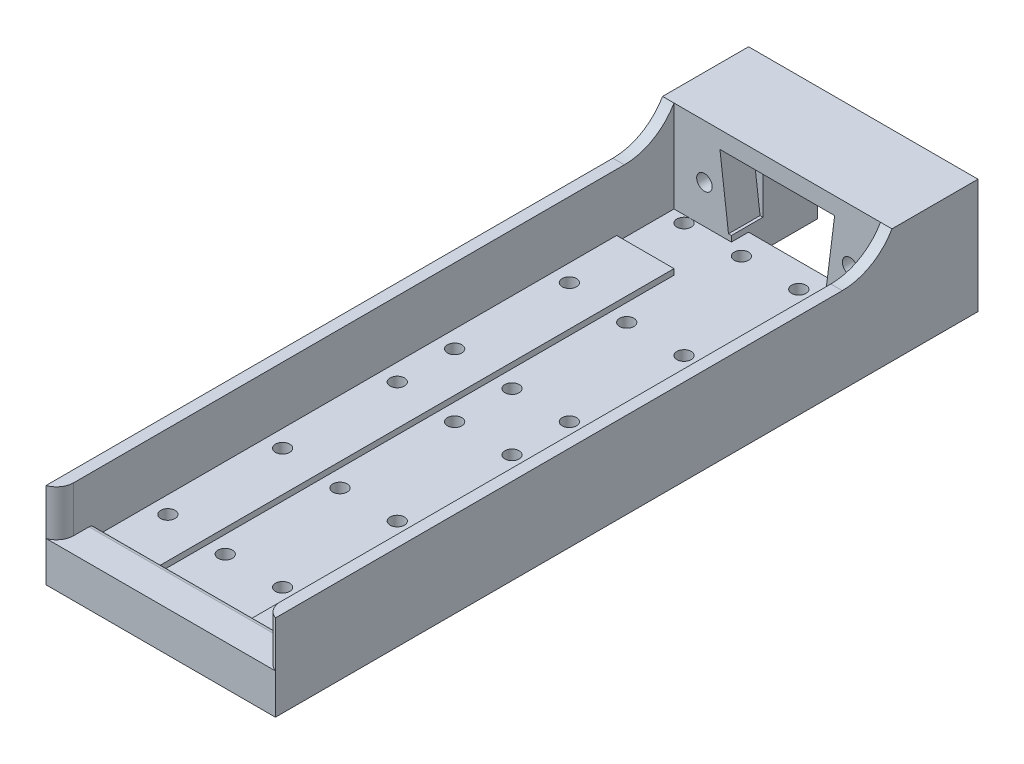
SolidWorks part; units mm, degrees
ref_plane "Front Plane" through (0, 0, 0) normal (0, 0, 1) x (1, 0, 0)
ref_plane "Top Plane" through (0, 0, 0) normal (0, 1, 0) x (1, 0, 0)
ref_plane "Right Plane" through (0, 0, 0) normal (1, 0, 0) x (0, 0, -1)
sketch "Esquisse1" plane through (0, 0, 0) normal (0, 0, 1) x (1, 0, 0)
  line L0 (18, 15) -> (20, 15)
  line L1 (20, 15) -> (20, 0)
  line L2 (20, 0) -> (-20, 0)
  line L3 (-20, 0) -> (-20, 15)
  line L4 (-20, 15) -> (-18, 15)
  line L5 (-18, 15) -> (-18, 5)
  line L6 (-18, 5) -> (-8, 5)
  line L7 (18, 5) -> (18, 15)
  line L8 (-8, 5) -> (-8, 4)
  line L9 (-8, 4) -> (8, 4)
  line L10 (8, 4) -> (8, 5)
  line L11 (8, 5) -> (18, 5)
  point P13 (0, 0)
  point P14 (0, 0)
  dimension "D1" = 2
  dimension "D2" = 1
  dimension "D3" = 36
  dimension "D4" = 10
  dimension "D5" = 2
  dimension "D6" = 40
  dimension "D7" = 5
  dimension "D8" = 10
  dimension "D9" = 4
extrude "Main" add sketch "Esquisse1" along normal mid plane 122.5
fillet "Front Conge" radius 3 2 edges at (18, 10, 61.25) (-18, 10, 61.25)
ref_plane "PlaneForDSub" through (0, 0, -46.25) normal (0, 0, 1) x (1, 0, 0)
sketch "Esquisse11" plane through (0, 0, -46.25) normal (0, 0, -1) x (-1, 0, 0)
  line L0 (20, 15) -> (20, 0) construction
  line L1 (-20, 20) -> (-18, 20)
  line L2 (-20, 20) -> (-20, 5)
  line L3 (-20, 5) -> (-18, 5)
  line L4 (-18, 20) -> (-18, 5)
  line L5 (18, 20) -> (20, 20)
  line L6 (18, 20) -> (18, 5)
  line L7 (18, 5) -> (20, 5)
  line L8 (20, 20) -> (20, 5)
  line L9 (-20, 0) -> (-20, 5) construction
  dimension "D1" = 15
extrude "DSub-Extrusion Attachment" add sketch "Esquisse11" along normal blind 15
sketch "Esquisse12" plane through (0, 0, -46.25) normal (0, 0, -1) x (-1, 0, 0)
  line L1 (-20, 20) -> (20, 20)
  line L2 (-20, 20) -> (-20, 5)
  line L3 (-20, 5) -> (20, 5)
  line L4 (20, 20) -> (20, 5)
  line L6 (20, 5) -> (20, 0) construction
  line L7 (-8, 14.175) -> (8, 14.175)
  line L8 (-8, 14.175) -> (-8, 7.175)
  line L9 (-8, 7.175) -> (8, 7.175)
  line L10 (8, 14.175) -> (8, 7.175)
  line L11 (18, 15) -> (18, 5) construction
  line L12 (-18, 5) -> (-18, 15) construction
  line L13 (-20, 0) -> (-20, 5) construction
  circle A0 centre (-12.7, 10.675) radius 1.35
  circle A1 centre (12.7, 10.675) radius 1.35
  point P20 (0, 7.175)
  point P22 (-8, 10.675)
  point P27 (18, 10)
  dimension "D5" = 2.7
  dimension "D1" = 15
  dimension "D2" = 7
  dimension "D3" = 16
  dimension "D4" = 5.3
  dimension "D6" = 25.4
  dimension "D7" = 12.7
  dimension "D8" = 5.675
  dimension "D9" = 5.3
extrude "DSub-Extrusion" add sketch "Esquisse12" along normal blind 15
sketch "Esquisse13" plane through (0, 0, -46.25) normal (0, 0, 1) x (1, 0, 0)
  line L0 (-10, 17) -> (10, 17)
  line L2 (10, 17) -> (8.5, 5)
  line L3 (-20, 20) -> (20, 20) construction
  line L4 (8.5, 5) -> (-8.5, 5)
  line L5 (-8.5, 5) -> (-10, 17)
  line L6 (8, 5) -> (-8, 5) construction
  point P10 (0, 17)
  point P11 (0, 20)
  dimension "D1" = 17
  dimension "D2" = 20
  dimension "D4" = 12
extrude "DSub-Front Hole" cut sketch "Esquisse13" against normal blind 5.5
sketch "Esquisse14" plane through (0, 0, -61.25) normal (0, 0, -1) x (-1, 0, 0)
  circle A0 centre (-12.7, 10.675) radius 4.3
  circle A1 centre (12.7, 10.675) radius 4.3
  circle A2 centre (12.7, 10.675) radius 1.35 construction
  dimension "D1" = 8.6
extrude "Bottom Hole" cut sketch "Esquisse14" against normal blind 2
sketch "Sketch7" plane through (0, 5, 0) normal (0, 1, 0) x (1, 0, 0)
  line L0 (-18, -58.4216) -> (-18, 46.25) construction
  line L1 (-18, 36.25) -> (18, 36.25)
  line L2 (-18, 36.25) -> (-18, 46.25)
  line L3 (-18, 46.25) -> (18, 46.25)
  line L4 (18, 36.25) -> (18, 46.25)
  point P6 (18, 46.25)
  dimension "D1" = 10
extrude "DSubBottomHole" cut sketch "Sketch7" against normal up to surface (1 mm away) up to face at (0, 4, 0)
fillet "Congé4" radius 10 2 edges at (-19, 15, -46.25) (19, 15, -46.25)
sketch "Sketch4" plane through (-20, 0, 0) normal (-1, 0, 0) x (0, 0, 1)
  line L0 (-46.25, -3.85) -> (-46.25, 3.85) construction
  line L1 (54.75, 7) -> (61.25, 7)
  line L2 (54.75, 7) -> (54.75, 0)
  line L3 (54.75, 0) -> (61.25, 0)
  line L4 (61.25, 7) -> (61.25, 0)
  dimension "D1" = 101
  dimension "D2" = 7
extrude "BottomStop" add sketch "Sketch4" against normal up to surface (40 mm away) up to face at (20, 10.5485, -3.3228)
fillet "Fillet1" radius 1 2 edges at (0, 4, 54.75) (0, 7, 54.75)
sketch "Sketch5" plane through (0, 0, 0) normal (0, -1, 0) x (-1, 0, 0)
  line L0 (20, 61.25) -> (-20, 61.25) construction
  line L1 (8, 61.25) -> (-8, 61.25)
  line L2 (8, 61.25) -> (8, 49.25)
  line L3 (8, 49.25) -> (-8, 49.25)
  line L4 (-8, 61.25) -> (-8, 49.25)
  line L5 (0, 55) -> (0, -55) construction
  point P5 (0, 61.25)
  point P6 (0, 0)
  point P8 (1.6731, 32.6524)
  point P9 (0, 61.6165)
  point P10 (0, 61.3939)
  point P13 (0, 0)
  point P14 (0, 61.25)
  dimension "D1" = 16
  dimension "D2" = 12
extrude "Cut-Extrude1" cut sketch "Sketch5" against normal up to surface (14.175 mm away) up to face at (0, 14.175, -56.5)
sketch "Sketch6" plane through (0, 0, 0) normal (0, -1, 0) x (-1, 0, 0)
  line L0 (0, 55) -> (0, -55) construction
  line L2 (-55, 0) -> (55, 0) construction
  circle A0 centre (15, -45) radius 1.25
  point P2 (0, 0)
  dimension "D1" = 2.5
  dimension "D2" = 15
  dimension "D3" = 45
extrude "FixHole" cut sketch "Sketch6" against normal through all
pattern_linear "LPattern1" count 3 spacing 20 along (0, 0, -1) count 4 spacing 10 along (1, 0, 0) of "FixHole"
mirror "Mirror1" about plane through (0, 0, 0) normal (0, 0, 1) of "LPattern1"
